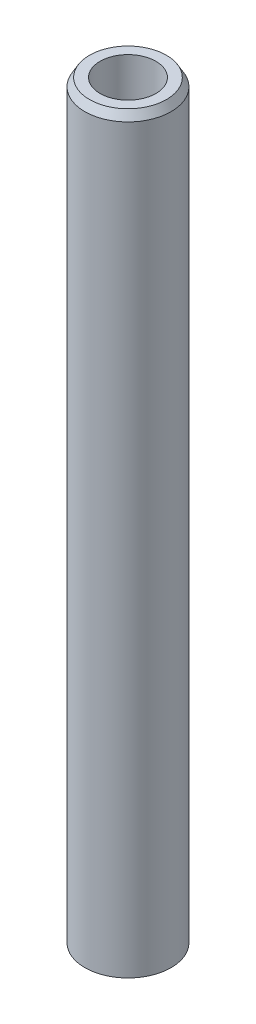
SolidWorks part; units mm, degrees
ref_plane "Front Plane" through (0, 0, 0) normal (0, 0, 1) x (1, 0, 0)
ref_plane "Top Plane" through (0, 0, 0) normal (0, 1, 0) x (1, 0, 0)
ref_plane "Right Plane" through (0, 0, 0) normal (1, 0, 0) x (0, 0, -1)
sketch "Sketch1" plane through (0, 0, 0) normal (0, 1, 0) x (1, 0, 0)
  circle A0 centre (0, 0) radius 22.5
  dimension "SHAFT_OD" = 45
extrude "Boss-Extrude1" add sketch "Sketch1" along normal blind 393.4267
sketch "Sketch2" plane through (0, 0, 0) normal (0, 1, 0) x (1, 0, 0)
  circle A0 centre (0, 0) radius 14.5708
  dimension "BORE_D" = 29.1415
extrude "Cut-Extrude1" cut sketch "Sketch2" along normal through all
chamfer "Chamfer1" distance 4.2352 angle 30 2 edges at (0, 393.4267, 22.5) (0, 0, 22.5) first distance on face at (0, 393.4267, 22.5) first distance on face at (0, 0, 14.5708)
